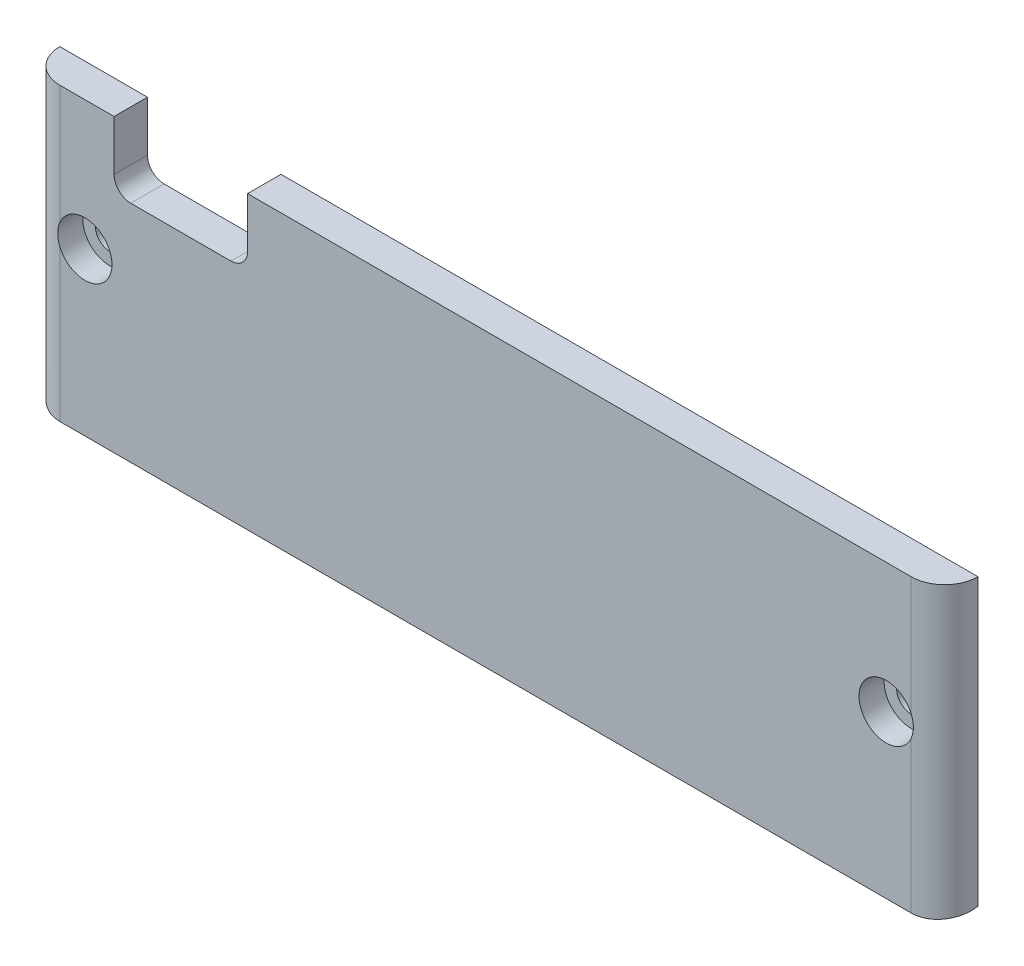
SolidWorks part; units mm, degrees
ref_plane "Plan de face" through (0, 0, 0) normal (0, 0, 1) x (1, 0, 0)
ref_plane "Plan de dessus" through (0, 0, 0) normal (0, 1, 0) x (1, 0, 0)
ref_plane "Plan de droite" through (0, 0, 0) normal (1, 0, 0) x (0, 0, -1)
sketch "Esquisse1" plane through (0, 0, 0) normal (0, 0, 1) x (1, 0, 0)
  line L1 (0, 0) -> (110, 0)
  line L2 (0, 0) -> (0, 34.19)
  line L3 (0, 34.19) -> (110, 34.19)
  line L4 (110, 0) -> (110, 34.19)
  dimension "D1" = 34.19
  dimension "D2" = 110
extrude "Boss.-Extru.1" add sketch "Esquisse1" along normal blind 4
sketch "Esquisse2" plane through (110, 0, 0) normal (1, 0, 0) x (0, 0, -1)
  line L0 (0, 0) -> (-4, 0)
  line L1 (-4, 0) -> (-4, -0.7053)
  line L2 (-4, -0.7053) -> (0, 0)
  dimension "D1" = 10
extrude "Boss.-Extru.2" add sketch "Esquisse2" against normal blind 110
sketch "Esquisse3" plane through (0, 0, 4) normal (0, 0, 1) x (1, 0, 0)
  line L0 (110, -0.7053) -> (110, 34.19) construction
  line L1 (0, 34.19) -> (0, -0.7053) construction
  line L2 (110, 34.19) -> (0, 34.19) construction
  circle A0 centre (7, 18.69) radius 1.75
  circle A1 centre (103, 18.69) radius 1.75
  dimension "D1" = 3.5
  dimension "D2" = 3.5
  dimension "D3" = 7
  dimension "D4" = 7
  dimension "D5" = 15.5
  dimension "D6" = 15.5
extrude "Enlèv. mat.-Extru.1" cut sketch "Esquisse3" against normal blind 4
sketch "Esquisse4" plane through (0, 0, 4) normal (0, 0, 1) x (1, 0, 0)
  circle A0 centre (7, 18.69) radius 3.25
  circle A1 centre (103, 18.69) radius 3.25
  dimension "D1" = 6.5
  dimension "D2" = 6.5
extrude "Enlèv. mat.-Extru.2" cut sketch "Esquisse4" against normal blind 3
sketch "Esquisse5" plane through (0, 0, 4) normal (0, 0, 1) x (1, 0, 0)
  line L2 (10.5, 30.19) -> (10.5, 28.19)
  line L3 (12.5, 26.19) -> (24.5, 26.19)
  line L4 (26.5, 30.19) -> (26.5, 28.19)
  line L5 (0, 34.19) -> (0, -0.7053) construction
  line L6 (10.5, 30.19) -> (10.5, 34.19)
  line L7 (110, 34.19) -> (0, 34.19) construction
  line L8 (10.5, 34.19) -> (26.5, 34.19)
  line L9 (26.5, 34.19) -> (26.5, 30.19)
  arc A1 (24.5, 26.19) -> (26.5, 28.19) centre (24.5, 28.19) ccw
  arc A2 (12.5, 26.19) -> (10.5, 28.19) centre (12.5, 28.19) cw
  dimension "D3" = 16
  dimension "D5" = 10.5
extrude "Enlèv. mat.-Extru.3" cut sketch "Esquisse5" against normal blind 4
fillet "Congé1" radius 4 2 edges at (0, 16.7423, 4) (110, 16.7423, 4)
